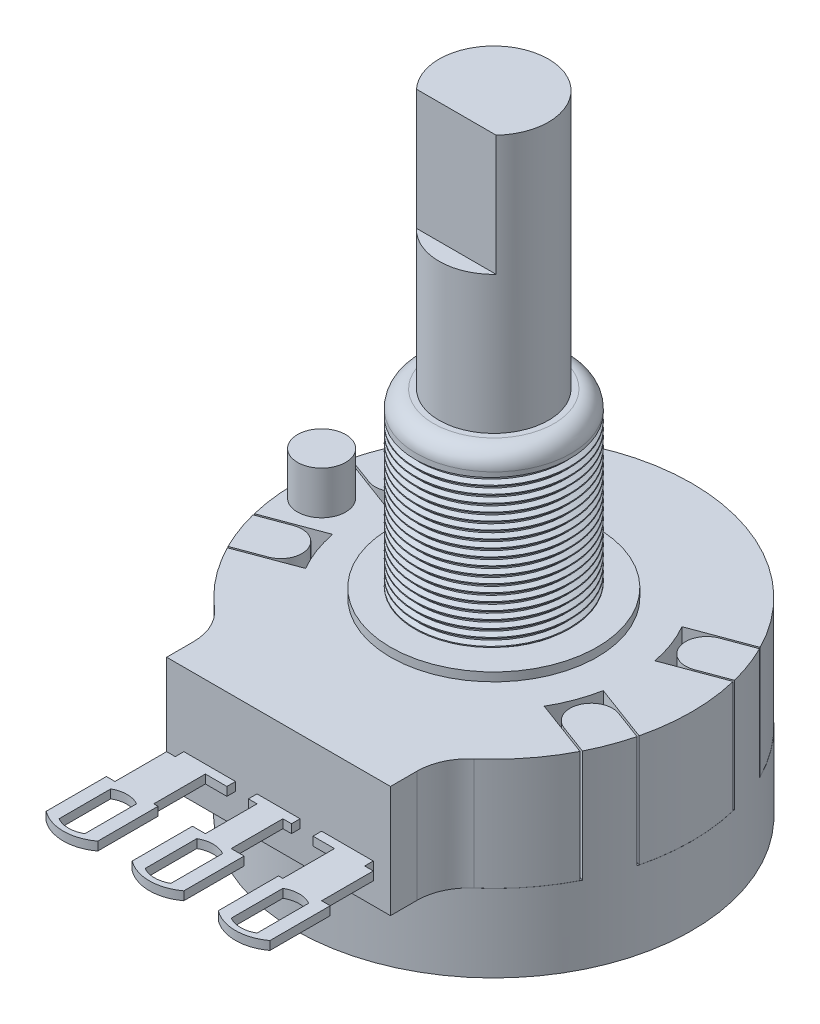
SolidWorks part; units mm, degrees
ref_plane "Front Plane" through (0, 0, 0) normal (0, 0, 1) x (1, 0, 0)
ref_plane "Top Plane" through (0, 0, 0) normal (0, 1, 0) x (1, 0, 0)
ref_plane "Right Plane" through (0, 0, 0) normal (1, 0, 0) x (0, 0, -1)
sketch "Sketch1" plane through (0, 0, 0) normal (0, 1, 0) x (1, 0, 0)
  circle A0 centre (0, 0) radius 11.5
  dimension "D1" = 23
extrude "Boss-Extrude1" add sketch "Sketch1" against normal blind 4.5
sketch "Sketch2" plane through (0, 0, 0) normal (0, 1, 0) x (1, 0, 0)
  line L0 (0, -17.325) -> (0, 17.325) construction
  line L4 (-6.5, -9.4868) -> (-6.5, -12.5)
  line L5 (-6.5, -12.5) -> (6.5, -12.5)
  line L6 (6.5, -9.4868) -> (6.5, -12.5)
  line L7 (-12.65, 0) -> (12.65, 0) construction
  arc A0 (6.5, -9.4868) -> (-6.5, -9.4868) centre (0, 0) ccw
  dimension "D1" = 12.5
  dimension "D4" = 11.5
  dimension "D2" = 6.5
  dimension "D3" = 6.5
extrude "Boss-Extrude2" add sketch "Sketch2" along normal blind 6.5
sketch "Sketch3" plane through (0, 6.5, 0) normal (0, 1, 0) x (1, 0, 0)
  circle A0 centre (0, 0) radius 6
  dimension "D1" = 12
extrude "Boss-Extrude3" add sketch "Sketch3" along normal blind 0.5
sketch "Sketch5" plane through (0, 7, 0) normal (0, 1, 0) x (1, 0, 0)
  circle A0 centre (0, 0) radius 4.5
  dimension "D1" = 9
extrude "Boss-Extrude4" add sketch "Sketch5" along normal blind 10
sketch "Sketch6" plane through (0, 17, 0) normal (0, 1, 0) x (1, 0, 0)
  circle A0 centre (0, 0) radius 3.175
  dimension "D1" = 6.35
extrude "Boss-Extrude5" add sketch "Sketch6" along normal blind 15 separate body contours A0
sketch "Sketch7" plane through (0, 32, 0) normal (0, 1, 0) x (1, 0, 0)
  line L0 (0, -2.175) -> (0, -3.175) construction
  line L1 (-2.313, -2.175) -> (2.313, -2.175)
  circle A0 centre (0, 0) radius 3.175
  dimension "D1" = 1
  dimension "D2" = 4.626
extrude "Cut-Extrude2" cut sketch "Sketch7" against normal blind 7 and the other way through all flip side to cut contours L1
sketch "Sketch8" plane through (0, 0, 12.5) normal (0, 0, 1) x (1, 0, 0)
  line L0 (0, 6.5) -> (0, 2.25)
  line L1 (6, 6.5) -> (-6, 6.5) construction
  dimension "D1" = 4.25
ref_plane "Plane1" through (0, 2.25, 0) normal (0, 1, 0) x (1, 0, 0)
sketch "Sketch10" plane through (0, 2.25, 0) normal (0, 1, 0) x (1, 0, 0)
  line L0 (0.75, -16) -> (1.5, -16)
  line L1 (0, -12.5) -> (0, -20) construction
  line L2 (-6.5, -12.5) -> (6.5, -12.5) construction
  line L3 (-1.25, -12.5) -> (1.25, -12.5)
  line L4 (-1.25, -12.5) -> (-1.25, -13)
  line L5 (-1.25, -13) -> (-0.75, -13)
  line L6 (1.25, -12.5) -> (1.25, -13)
  line L8 (-0.75, -13) -> (-0.75, -16)
  line L10 (0.75, -13) -> (0.75, -16)
  line L11 (-1.5, -16) -> (-0.75, -16)
  line L12 (-1.5, -16) -> (-1.5, -19.5)
  line L14 (1.5, -16) -> (1.5, -19.5)
  line L15 (0.75, -13) -> (1.25, -13)
  line L16 (-6, -13) -> (-6, -16)
  line L17 (-3.75, -16) -> (-3.5, -16)
  line L18 (-3.5, -16) -> (-3.5, -19.5)
  line L19 (-5, -12.5) -> (-5, -20) construction
  line L20 (-6.5, -16) -> (-6, -16)
  line L21 (-5.5, -12.5) -> (-5.5, -13)
  line L22 (-6.5, -16) -> (-6.5, -19.5)
  line L23 (-5.5, -12.5) -> (-2.5, -12.5)
  line L24 (-3.75, -13) -> (-2.5, -13)
  line L25 (-2.5, -12.5) -> (-2.5, -13)
  line L26 (-5.5, -13) -> (-6, -13)
  line L27 (-3.75, -13) -> (-3.75, -16)
  line L28 (3.75, -13) -> (3.75, -16)
  line L29 (6, -16) -> (6.5, -16)
  line L30 (6.5, -16) -> (6.5, -19.5)
  line L31 (5, -12.5) -> (5, -20) construction
  line L32 (3.5, -16) -> (3.75, -16)
  line L33 (2.5, -12.5) -> (2.5, -13)
  line L34 (3.5, -16) -> (3.5, -19.5)
  line L35 (2.5, -12.5) -> (5.5, -12.5)
  line L36 (6, -13) -> (5.5, -13)
  line L37 (5.5, -12.5) -> (5.5, -13)
  line L38 (2.5, -13) -> (3.75, -13)
  line L39 (6, -13) -> (6, -16)
  arc A0 (-1.5, -19.5) -> (1.5, -19.5) centre (0, -17.5) ccw
  arc A3 (-6.5, -19.5) -> (-3.5, -19.5) centre (-5, -17.5) ccw
  arc A4 (6.5, -19.5) -> (3.5, -19.5) centre (5, -17.5) cw
  point P18 (0, -20)
  point P37 (-5, -20)
  point P51 (-2.5, -12.75)
  point P53 (5, -20)
  dimension "D34" = 7.5
  dimension "D35" = 7.5
  dimension "D32" = 7.5
  dimension "D36" = 3
  dimension "D1" = 1.25
  dimension "D2" = 1.25
  dimension "D3" = 0.5
  dimension "D4" = 0.75
  dimension "D5" = 0.75
  dimension "D6" = 3
  dimension "D7" = 7.5
  dimension "D8" = 3.5
  dimension "D9" = 1.5
  dimension "D10" = 1.5
  dimension "D11" = 7.5
  dimension "D12" = 5
  dimension "D13" = 5
  dimension "D14" = 1.5
  dimension "D15" = 1.5
  dimension "D16" = 1.5
  dimension "D17" = 1.5
  dimension "D18" = 1
  dimension "D19" = 1.25
  dimension "D20" = 1
  dimension "D21" = 1.25
  dimension "D22" = 3
  dimension "D23" = 0.5
  dimension "D24" = 3
  dimension "D25" = 0.5
  dimension "D26" = 0.5
  dimension "D27" = 0.5
  dimension "D28" = 3
  dimension "D29" = 3
  dimension "D30" = 3.5
  dimension "D31" = 3.5
  dimension "D33" = 7.5
  dimension "D37" = 3
  dimension "D38" = 3
extrude "Boss-Extrude6" add sketch "Sketch10" against normal blind 0.5
sketch "Sketch16" plane through (0, 2.25, 0) normal (0, 1, 0) x (1, 0, 0)
  line L2 (-0.75, -16.5) -> (-0.75, -19.5)
  line L4 (0.75, -16.5) -> (0.75, -19.5)
  line L5 (-1.5, -16) -> (-1.5, -19.5) construction
  line L6 (-6.5, -12.5) -> (6.5, -12.5) construction
  line L7 (-5.75, -16.5) -> (-5.75, -19.5)
  line L8 (-4.25, -16.5) -> (-4.25, -19.5)
  line L9 (4.25, -16.5) -> (4.25, -19.5)
  line L10 (5.75, -16.5) -> (5.75, -19.5)
  line L11 (-6.5, -16) -> (-6.5, -19.5) construction
  line L12 (3.5, -16) -> (3.5, -19.5) construction
  arc A0 (-0.75, -16.5) -> (0.75, -16.5) centre (0, -17.799) cw
  arc A1 (-0.75, -19.5) -> (0.75, -19.5) centre (0, -18.201) ccw
  arc A2 (-5.75, -19.5) -> (-4.25, -19.5) centre (-5, -18.201) ccw
  arc A3 (-5.75, -16.5) -> (-4.25, -16.5) centre (-5, -17.799) cw
  arc A4 (4.25, -19.5) -> (5.75, -19.5) centre (5, -18.201) ccw
  arc A5 (4.25, -16.5) -> (5.75, -16.5) centre (5, -17.799) cw
  dimension "D5" = 1.5
  dimension "D7" = 1.5
  dimension "D13" = 1.5
  dimension "D14" = 1.5
  dimension "D15" = 1.5
  dimension "D16" = 1.5
  dimension "D1" = 4
  dimension "D2" = 1.5
  dimension "D3" = 3
  dimension "D4" = 0.75
  dimension "D6" = 4
  dimension "D8" = 3
  dimension "D9" = 3
  dimension "D10" = 3
  dimension "D11" = 3
  dimension "D12" = 3
  dimension "D17" = 0.75
  dimension "D18" = 0.75
  dimension "D19" = 4
  dimension "D20" = 4
  dimension "D21" = 4
  dimension "D22" = 4
  dimension "D23" = 1.5
  dimension "D24" = 1.5
extrude "Cut-Extrude3" cut sketch "Sketch16" against normal up to next (0.5 mm away)
sketch "Sketch23" plane through (0, 6.5, 0) normal (0, 1, 0) x (1, 0, 0)
  line L0 (-10, 0) -> (0, 0) construction
  circle A0 centre (-10, 0) radius 1.4
  dimension "D2" = 2.8
  dimension "D1" = 10
extrude "Boss-Extrude7" add sketch "Sketch23" along normal blind 2.5
sketch "Sketch24" plane through (0, 6.5, 0) normal (0, 1, 0) x (1, 0, 0)
  line L0 (-7.8581, -1.5) -> (-7.8581, 1.5) construction
  line L1 (-6.9282, 4) -> (-6.9282, -4) construction
  line L2 (7.8581, 1.5) -> (7.8581, -1.5) construction
  line L3 (6.9282, 4) -> (6.9282, -4) construction
  line L4 (-6.9282, -4) -> (-10.2408, -5.2322)
  line L5 (-7.8581, -1.5) -> (-11.1707, -2.7322)
  line L6 (-7.8581, 1.5) -> (-11.1707, 2.7322)
  line L7 (-6.9282, 4) -> (-10.2408, 5.2322)
  line L8 (6.9282, 4) -> (10.2408, 5.2322)
  line L10 (7.8581, -1.5) -> (11.1707, -2.7322)
  line L11 (6.9282, -4) -> (10.2408, -5.2322)
  line L12 (7.8581, 1.5) -> (11.1707, 2.7322)
  arc A0 (6.9282, -4) -> (7.8581, -1.5) centre (0, 0) ccw
  arc A1 (10.2408, -5.2322) -> (11.1707, -2.7322) centre (0, 0) ccw
  arc A2 (-6.9282, 4) -> (-7.8581, 1.5) centre (0, 0) ccw
  arc A3 (-10.2408, 5.2322) -> (-11.1707, 2.7322) centre (0, 0) ccw
  arc A4 (-11.1707, -2.7322) -> (-10.2408, -5.2322) centre (0, 0) ccw
  arc A5 (11.1707, 2.7322) -> (10.2408, 5.2322) centre (0, 0) ccw
  arc A6 (-7.8581, -1.5) -> (-6.9282, -4) centre (0, 0) ccw
  arc A7 (7.8581, 1.5) -> (6.9282, 4) centre (0, 0) ccw
  dimension "D1" = 16
  dimension "D2" = 23
  dimension "D5" = 3
  dimension "D6" = 3
  dimension "D3" = 8
  dimension "D4" = 8
  dimension "D7" = 3.5344
  dimension "D8" = 3.5344
  dimension "D9" = 3.5344
  dimension "D10" = 3.5344
  dimension "D11" = 3.5344
  dimension "D12" = 3.5344
  dimension "D13" = 3.5344
  dimension "D14" = 3.5344
extrude "Cut-Extrude4" cut sketch "Sketch24" against normal blind 6.5
fillet "Fillet5" radius 1 1 edges at (0, 17, 4.5)
fillet "Fillet7" radius 3 2 edges at (6.5, 3.25, 9.4868) (-6.5, 3.25, 9.4868)
thread "Thread5" pitch 0.45 start angle 2, offset 0, length 10, pitch 0.45, diameter 9
ref_plane "Plane7" through (-4.4973, 16, -0.157) normal (-0.0349, 0, 0.9994) x (-0.9994, 0, -0.0349)
sketch "Thread Profile6" plane through (-4.4973, 16, -0.157) normal (-0.0349, 0, 0.9994) x (-0.9994, 0, -0.0349)
  line L0 (0, 0) -> (0, 0.45) construction
  line L11 (0, 0) -> (0, 0.3937)
  line L12 (0, 0.3937) -> (-0.2436, 0.2531)
  line L13 (-0.2436, 0.2531) -> (-0.2436, 0.1406)
  line L15 (-0.2436, 0.1406) -> (0, 0)
  line L17 (-0.2436, 0.1969) -> (0, 0.1969) construction
  point P2 (0, 0)
  dimension "Pitch" = 0.45
  dimension "Profile_Angle" = 60
  dimension "Profile_Land" = 0.1125
  dimension "Profile_Height" = 0.2436
sketch "Sketch37" [suppressed] plane through (0, -4.5, 0) normal (0, -1, 0) x (1, 0, 0)
  circle A0 centre (0, 0) radius 11.5
  dimension "D1" = 23
extrude "Cut-Extrude6" [suppressed] cut sketch "Sketch37" against normal up to vertex
sketch "Sketch40" [suppressed] plane through (0, 0, 0) normal (0, 1, 0) x (1, 0, 0)
  circle A0 centre (0, 0) radius 11.505
  dimension "D1" = 23.01
extrude "Boss-Extrude13" [suppressed] add sketch "Sketch40" against normal blind 4.5
sketch "Sketch42" [suppressed] plane through (0, 0, 0) normal (0, 1, 0) x (1, 0, 0)
  line L4 (11.1707, -2.7322) -> (7.8581, -1.5) construction
  line L6 (8.588, -4.5107) -> (10.2909, -5.1441)
  line L7 (9.4482, -2.1981) -> (11.1511, -2.8316)
  line L8 (6.9282, -4) -> (10.2408, -5.2322) construction
  line L14 (-10.2408, -5.2322) -> (-6.9282, -4) construction
  line L15 (-7.8581, -1.5) -> (-11.1707, -2.7322) construction
  line L16 (-9.4482, -2.1981) -> (-11.1511, -2.8316)
  line L17 (-8.588, -4.5107) -> (-10.2909, -5.1441)
  line L22 (-6.9282, 4) -> (-10.2408, 5.2322) construction
  line L23 (-11.1707, 2.7322) -> (-7.8581, 1.5) construction
  line L24 (-9.4482, 2.1981) -> (-11.1511, 2.8316)
  line L25 (-8.588, 4.5107) -> (-10.2909, 5.1441)
  line L33 (8.588, 4.5107) -> (10.2909, 5.1441)
  line L35 (10.2408, 5.2322) -> (6.9282, 4) construction
  line L36 (9.4482, 2.1981) -> (11.1511, 2.8316)
  line L37 (7.8581, 1.5) -> (11.1707, 2.7322) construction
  arc A0 (7.4206, -8.792) -> (-7.4206, -8.792) centre (0, 0) ccw construction
  arc A1 (9.4482, -2.1981) -> (8.588, -4.5107) centre (9.0181, -3.3544) ccw
  arc A2 (-8.588, -4.5107) -> (-9.4482, -2.1981) centre (-9.0181, -3.3544) ccw
  arc A3 (-7.8581, -1.5) -> (-6.9282, -4) centre (0, 0) ccw construction
  arc A4 (-9.4482, 2.1981) -> (-8.588, 4.5107) centre (-9.0181, 3.3544) ccw
  arc A5 (8.588, 4.5107) -> (9.4482, 2.1981) centre (9.0181, 3.3544) ccw
  arc A7 (-10.2909, 5.1441) -> (-11.1511, 2.8316) centre (0, 0) ccw
  arc A8 (11.1511, 2.8316) -> (10.2909, 5.1441) centre (0, 0) ccw
  arc A9 (10.2909, -5.1441) -> (11.1511, -2.8316) centre (0, 0) ccw
  arc A10 (-11.1511, -2.8316) -> (-10.2909, -5.1441) centre (0, 0) ccw
  dimension "D6" = 9.6217
  dimension "D7" = 9.6217
  dimension "D12" = 9.6217
  dimension "D1" = 0.1
  dimension "D2" = 0.1
  dimension "D3" = 9.6217
  dimension "D4" = 0.1
  dimension "D5" = 0.1
  dimension "D8" = 0.1
  dimension "D9" = 0.1
  dimension "D10" = 0.1
  dimension "D11" = 0.1
extrude "Boss-Extrude14" [suppressed] add sketch "Sketch42" along normal up to surface (6.5 mm away)
sketch "Sketch43" plane through (0, -4.5, 0) normal (0, -1, 0) x (1, 0, 0)
  circle A0 centre (0, 0) radius 11.5
extrude "Cut-Extrude7" cut sketch "Sketch43" against normal up to vertex (4.5 mm away)
sketch "Sketch44" plane through (0, 0, 0) normal (0, 1, 0) x (1, 0, 0)
  circle A0 centre (0, 0) radius 11.505
  dimension "D1" = 23.01
extrude "Boss-Extrude15" add sketch "Sketch44" against normal blind 4.5
sketch "Sketch45" plane through (0, 0, 0) normal (0, 1, 0) x (1, 0, 0)
  line L17 (10.2408, 5.2322) -> (6.9282, 4) construction
  line L18 (7.8581, 1.5) -> (11.1707, 2.7322) construction
  line L20 (6.9282, -4) -> (10.2408, -5.2322) construction
  line L21 (9.4482, 2.1981) -> (11.1511, 2.8316)
  line L22 (8.588, 4.5107) -> (10.2909, 5.1441)
  line L23 (-6.9282, 4) -> (-10.2408, 5.2322) construction
  line L24 (8.588, -4.5107) -> (10.2909, -5.1441)
  line L25 (9.4482, -2.1981) -> (11.1511, -2.8316)
  line L30 (-10.2408, -5.2322) -> (-6.9282, -4) construction
  line L31 (-7.8581, -1.5) -> (-11.1707, -2.7322) construction
  line L32 (-9.4482, -2.1981) -> (-11.1511, -2.8316)
  line L33 (-9.4482, 2.1981) -> (-11.1511, 2.8316)
  line L34 (-8.588, 4.5107) -> (-10.2909, 5.1441)
  line L35 (-8.588, -4.5107) -> (-10.2909, -5.1441)
  line L36 (-11.1707, 2.7322) -> (-7.8581, 1.5) construction
  line L37 (11.1707, -2.7322) -> (7.8581, -1.5) construction
  arc A0 (7.4206, -8.792) -> (-7.4206, -8.792) centre (0, 0) ccw construction
  arc A1 (8.588, 4.5107) -> (9.4482, 2.1981) centre (9.0181, 3.3544) ccw
  arc A2 (9.4482, -2.1981) -> (8.588, -4.5107) centre (9.0181, -3.3544) ccw
  arc A4 (-9.4482, 2.1981) -> (-8.588, 4.5107) centre (-9.0181, 3.3544) ccw
  arc A5 (-8.588, -4.5107) -> (-9.4482, -2.1981) centre (-9.0181, -3.3544) ccw
  arc A6 (-10.2909, 5.1441) -> (-11.1511, 2.8316) centre (0, 0) ccw
  arc A7 (11.1511, 2.8316) -> (10.2909, 5.1441) centre (0, 0) ccw
  arc A8 (10.2909, -5.1441) -> (11.1511, -2.8316) centre (0, 0) ccw
  arc A9 (-11.1511, -2.8316) -> (-10.2909, -5.1441) centre (0, 0) ccw
  dimension "D8" = 9.6217
  dimension "D9" = 9.6217
  dimension "D11" = 9.6217
  dimension "D12" = 9.6217
  dimension "D1" = 0.1
  dimension "D2" = 0.1
  dimension "D3" = 0.1
  dimension "D4" = 0.1
  dimension "D5" = 0.1
  dimension "D6" = 0.1
  dimension "D7" = 0.1
  dimension "D10" = 0.1
extrude "Boss-Extrude16" add sketch "Sketch45" along normal up to vertex
equation "\"L\"= 20'Assumed smallest size, must measure later. See Data Sheet"
equation "\"F\"= 7'Assumed smallest size, must measure later. see data sheet"
